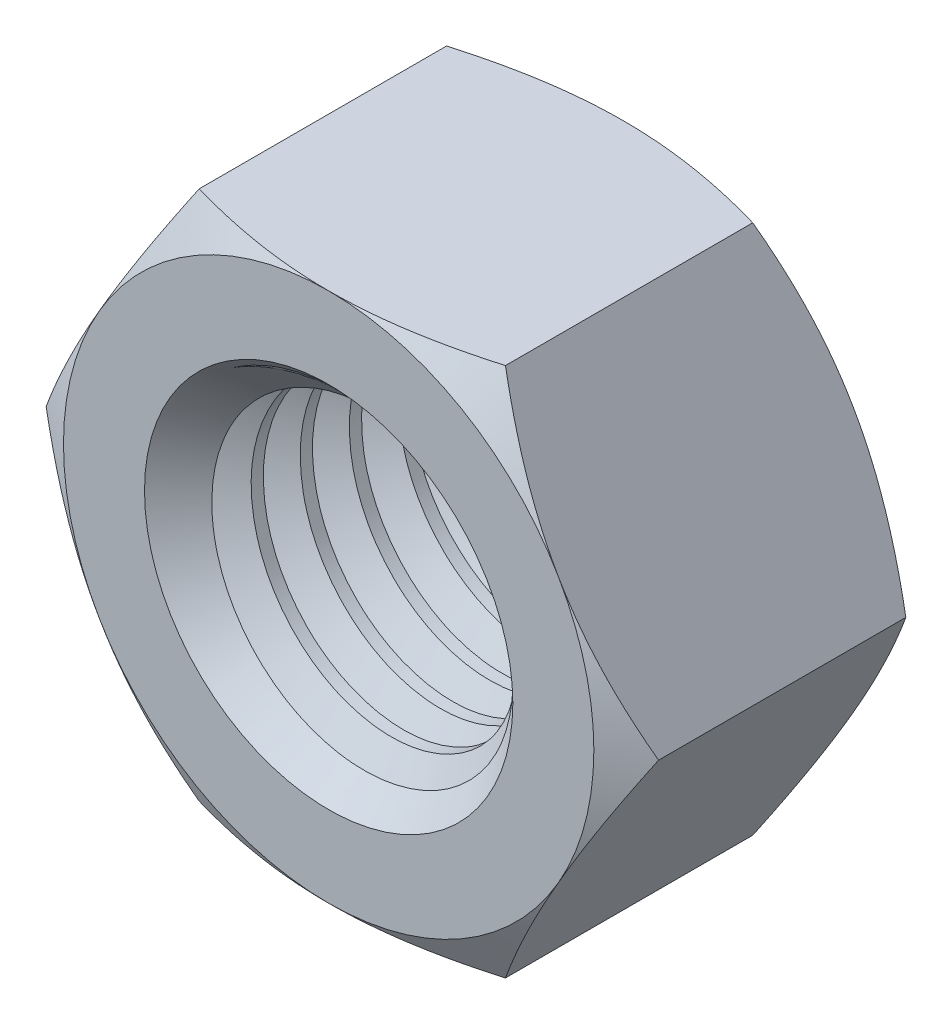
SolidWorks part; units mm, degrees
ref_plane "Front" through (0, 0, 0) normal (0, 0, 1) x (1, 0, 0)
ref_plane "Top" through (0, 0, 0) normal (0, 1, 0) x (1, 0, 0)
ref_plane "Right" through (0, 0, 0) normal (1, 0, 0) x (0, 0, -1)
sketch "Çizim1" plane through (0, 0, 0) normal (0, 0, 1) x (1, 0, 0)
  line L1 (15.5885, 0) -> (7.7942, 13.5)
  line L2 (7.7942, 13.5) -> (-7.7942, 13.5)
  line L3 (-7.7942, 13.5) -> (-15.5885, 0)
  line L4 (-15.5885, 0) -> (-7.7942, -13.5)
  line L5 (-7.7942, -13.5) -> (7.7942, -13.5)
  line L6 (7.7942, -13.5) -> (15.5885, 0)
  circle A0 centre (0, 0) radius 13.5 construction
  point P1 (0, 0)
  dimension "D1" = 27
extrude "Yükseklik-Ekstrüzyon1" add sketch "Çizim1" along normal blind 15
sketch "Çizim2" plane through (0, 0, 15) normal (0, 0, 1) x (1, 0, 0)
  circle A0 centre (0, 0) radius 13.5
extrude "Kes-Ekstrüzyon1" cut sketch "Çizim2" against normal blind 15 draft 60 flip side to cut
sketch "Çizim3" plane through (0, 0, 0) normal (0, 0, -1) x (-1, 0, 0)
  circle A0 centre (0, 0) radius 13.5
extrude "Kes-Ekstrüzyon2" cut sketch "Çizim3" against normal blind 15 draft 60 flip side to cut
sketch "Çizim4" plane through (0, 0, 15) normal (0, 0, 1) x (1, 0, 0)
  circle A0 centre (0, 0) radius 7.375
  dimension "D1" = 14.75
extrude "Kes-Ekstrüzyon3" cut sketch "Çizim4" against normal blind 25
chamfer "Pah1" distance 2 angle 45 2 edges at (7.375, 0, 0) (7.375, 0, 15)
sketch "Çizim5" plane through (0, 0, 15) normal (0, 0, 1) x (1, 0, 0)
  circle A0 centre (0, 0) radius 7.375
curve "Helis/Spiral1" pitch 2.5 height 18 radius 7.375 centre (0, 0, 15) axis (0, 0, -1) start towards (-1, 0, 0)
ref_plane "Düzlem1" through (-2.279, 7.014, -3) normal (0.9497, 0.3086, -0.0539) x (-0.0512, -0.0166, -0.9985)
sketch "Çizim6" plane through (-2.279, 7.014, -3) normal (0.9497, 0.3086, -0.0539) x (-0.0512, -0.0166, -0.9985)
  line L1 (0, 1.625) -> (-1.2025, -0.4577)
  line L3 (1.2025, -0.4577) -> (0, 1.625)
  line L4 (-1.2025, -0.4577) -> (1.2025, -0.4577)
  line L5 (0, -0.8125) -> (1.4073, -0.8125) [skipped]
  circle A0 centre (0, 0) radius 0.8125 construction
  dimension "D1" = 1.625
sweep "Kes-Süpür1" cut profiles "Çizim6" path "Helis/Spiral1" align with end faces yes
